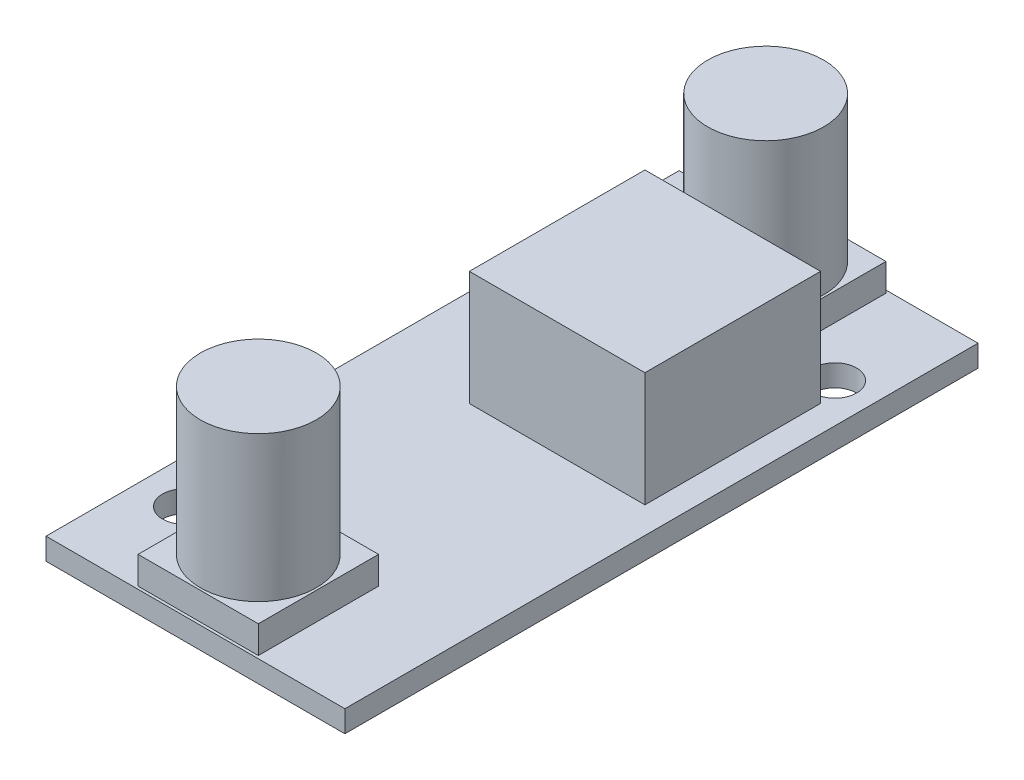
SolidWorks part; units mm, degrees
ref_plane "Front Plane" through (0, 0, 0) normal (0, 0, 1) x (1, 0, 0)
ref_plane "Top Plane" through (0, 0, 0) normal (0, 1, 0) x (1, 0, 0)
ref_plane "Right Plane" through (0, 0, 0) normal (1, 0, 0) x (0, 0, -1)
sketch "Sketch1" plane through (0, 0, 0) normal (0, 1, 0) x (1, 0, 0)
  line L1 (-10.315, 21.85) -> (10.315, 21.85)
  line L2 (-10.315, 21.85) -> (-10.315, -21.85)
  line L3 (-10.315, -21.85) -> (10.315, -21.85)
  line L4 (10.315, 21.85) -> (10.315, -21.85)
  line L5 (-10.315, 21.85) -> (10.315, -21.85) construction
  line L6 (-10.315, -21.85) -> (10.315, 21.85) construction
  point P0 (0, 0)
  dimension "D1" = 20.63
  dimension "D2" = 43.7
extrude "Boss-Extrude1" add sketch "Sketch1" along normal blind 1.5
sketch "Sketch2" plane through (0, 1.5, 0) normal (0, 1, 0) x (1, 0, 0)
  line L0 (7.605, 21.85) -> (7.605, 14.68) construction
  line L1 (10.315, 21.85) -> (-10.315, 21.85) construction
  line L2 (10.315, 14.68) -> (7.605, 14.68) construction
  line L3 (10.315, -21.85) -> (10.315, 21.85) construction
  line L4 (-7.315, -21.85) -> (-7.315, -15.31) construction
  line L5 (-10.315, -21.85) -> (10.315, -21.85) construction
  line L6 (-10.315, -15.31) -> (-7.315, -15.31) construction
  line L7 (-10.315, 21.85) -> (-10.315, -21.85) construction
  circle A0 centre (7.605, 14.68) radius 1.5
  circle A1 centre (-7.315, -15.31) radius 1.5
  dimension "D3" = 6.54
  dimension "D1" = 2.71
  dimension "D2" = 7.17
  dimension "D4" = 3
extrude "Cut-Extrude1" cut sketch "Sketch2" against normal blind 1.5
sketch "Sketch3" plane through (0, 1.5, 0) normal (0, 1, 0) x (1, 0, 0)
  line L0 (0, -21.85) -> (0, -21.66) construction
  line L1 (-10.315, -21.85) -> (10.315, -21.85) construction
  line L2 (0, -21.66) -> (-4.15, -21.66)
  line L3 (-4.15, -21.66) -> (-4.15, -13.36)
  line L4 (-4.15, -13.36) -> (4.15, -13.36)
  line L5 (4.15, -13.36) -> (4.15, -21.66)
  line L6 (4.15, -21.66) -> (0, -21.66)
  dimension "D1" = 8.3
  dimension "D2" = 8.3
  dimension "D3" = 0.19
extrude "Boss-Extrude2" add sketch "Sketch3" along normal blind 1.9
sketch "Sketch4" plane through (0, 3.4, 0) normal (0, 1, 0) x (1, 0, 0)
  line L0 (-4.15, -13.36) -> (4.15, -21.66) construction
  circle A0 centre (0, -17.51) radius 4
extrude "Boss-Extrude3" add sketch "Sketch4" along normal blind 10.04
ref_point "Point1"
ref_point "Point2"
ref_axis "Axis1" through (0, 0.75, -21.85) along (0, 0, 1)
ref_plane "Plane1" through (0, 0, 0) normal (-1, 0, 0) x (0, 0, 1)
ref_point "Point3"
ref_point "Point4"
ref_axis "Axis2" through (-10.315, 0.75, 0) along (1, 0, 0)
ref_plane "Plane2" through (0, 0, 0) normal (0, 0, 1) x (1, 0, 0)
mirror "Mirror1" about plane through (0, 0, 0) normal (0, 0, 1) of "Boss-Extrude3", "Boss-Extrude2"
sketch "Sketch5" plane through (0, 1.5, 0) normal (0, 1, 0) x (1, 0, 0)
  line L0 (5.119, 21.85) -> (5.119, 12.81) construction
  line L1 (10.315, 21.85) -> (-10.315, 21.85) construction
  line L2 (10.315, 8.5456) -> (8.485, 8.5456) construction
  line L3 (-3.635, 12.81) -> (8.485, 12.81)
  line L4 (-3.635, 12.81) -> (-3.635, 0.69)
  line L5 (-3.635, 0.69) -> (8.485, 0.69)
  line L6 (8.485, 12.81) -> (8.485, 0.69)
  line L7 (-3.635, 12.81) -> (8.485, 0.69) construction
  line L8 (-3.635, 0.69) -> (8.485, 12.81) construction
  line L9 (10.315, -21.85) -> (10.315, 21.85) construction
  point P4 (2.425, 6.75)
  dimension "D1" = 12.12
  dimension "D2" = 12.12
  dimension "D3" = 9.04
  dimension "D4" = 1.83
extrude "Boss-Extrude4" add sketch "Sketch5" along normal blind 7.9
